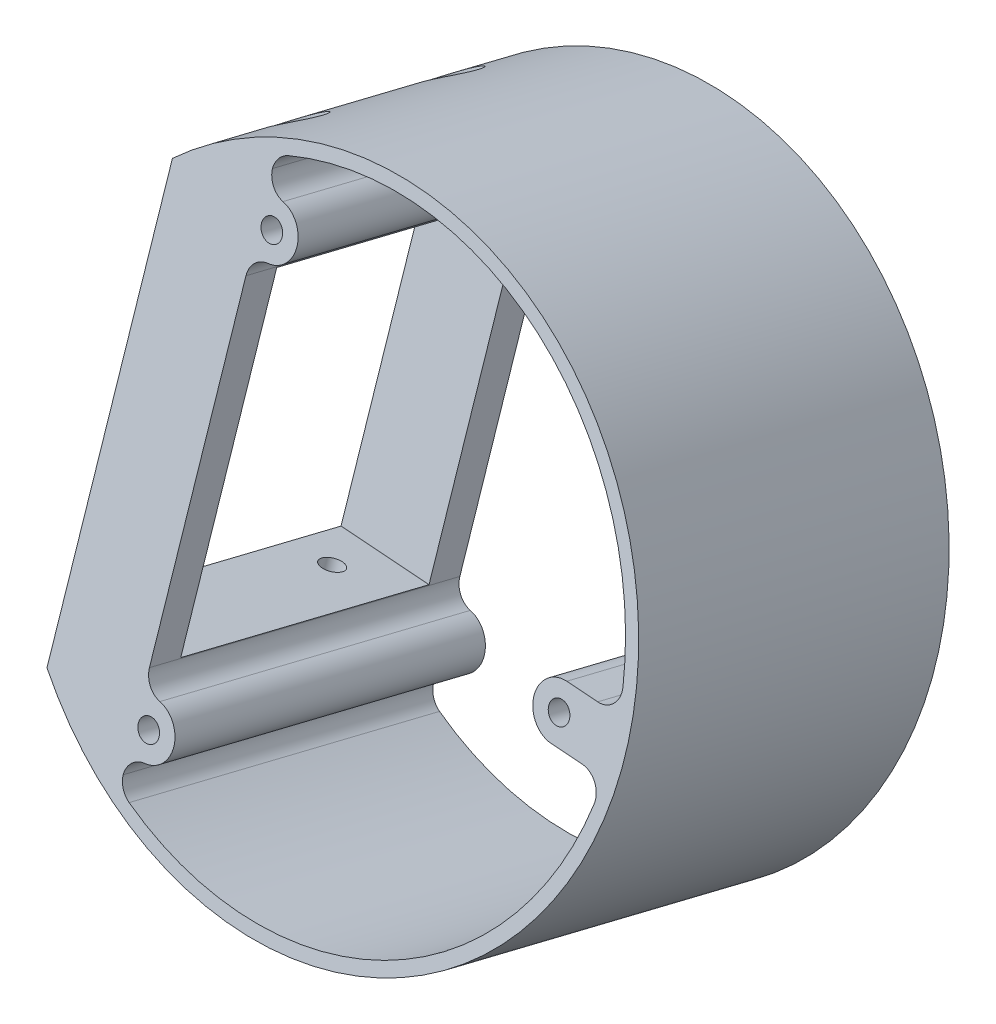
SolidWorks part; units mm, degrees
ref_plane "Front Plane" through (0, 0, 0) normal (0, 0, 1) x (1, 0, 0)
ref_plane "Top Plane" through (0, 0, 0) normal (0, 1, 0) x (1, 0, 0)
ref_plane "Right Plane" through (0, 0, 0) normal (1, 0, 0) x (0, 0, -1)
sketch "Sketch1" plane through (0, -11.0837, -45.1368) normal (0, -0.2385, -0.9711) x (-1, 0, 0)
  line L0 (190.5723, 100.5223) -> (195.806, 17.0201)
  line L1 (188.6521, 99.1867) -> (188.972, 94.0836)
  line L2 (133.8057, 55.0492) -> (125.3224, 54.5175) construction
  line L3 (133.5555, 59.0414) -> (125.248, 58.5207)
  line L4 (134.0559, 51.057) -> (125.7484, 50.5363)
  line L5 (189.4054, 87.169) -> (192.9808, 30.1232)
  line L6 (188.6521, 99.1867) -> (193.7341, 18.1055) construction
  line L7 (193.4142, 23.2086) -> (193.7341, 18.1055)
  arc A0 (188.972, 94.0836) -> (189.4054, 87.169) centre (187.1926, 90.5012) ccw
  circle A1 centre (191.2015, 26.5408) radius 1.65
  circle A2 centre (191.2015, 26.5408) radius 1.65
  circle A3 centre (133.8057, 55.0492) radius 1.65
  circle A4 centre (133.8057, 55.0492) radius 1.65
  circle A5 centre (187.1926, 90.5012) radius 1.65
  circle A6 centre (187.1926, 90.5012) radius 1.65
  arc A7 (192.9808, 30.1232) -> (193.4142, 23.2086) centre (191.2015, 26.5408) ccw
  arc A8 (134.0559, 51.057) -> (133.5555, 59.0414) centre (133.8057, 55.0492) ccw
  circle A9 centre (170.7333, 57.3637) radius 47.5 construction
  arc A10 (190.5723, 100.5223) -> (195.806, 17.0201) centre (170.7333, 57.3637) ccw
  arc A11 (188.6521, 99.1867) -> (125.248, 58.5207) centre (170.7333, 57.3637) ccw
  arc A12 (125.7484, 50.5363) -> (193.7341, 18.1055) centre (170.7333, 57.3637) ccw
  arc A13 (188.6521, 99.1867) -> (193.7341, 18.1055) centre (170.7333, 57.3637) ccw construction
  dimension "D4" = 8
  dimension "D1" = 0
  dimension "D2" = 0
  dimension "D3" = 0
  dimension "D5" = 2
extrude "Boss-Extrude1" add sketch "Sketch1" along normal blind 50
fillet "Fillet1" radius 3 8 edges at (-125.7484, 32.0328, -81.4671) (-125.248, 39.7867, -83.3711) (-188.972, 74.3236, -91.852) (-189.4054, 67.6085, -90.203) (-188.6521, 79.2796, -93.0689) (-192.9808, 12.2086, -76.5991) (-193.4142, 5.4935, -74.9501) (-193.7341, 0.5376, -73.7332)
sketch "Sketch2" plane through (-196.1024, 11.9366, -2.9311) normal (-0.998, 0.0607, -0.0149) x (-0.0122, -0.4224, -0.9063)
  line L0 (36.5364, -54.7188) -> (85.5823, -64.4399) construction
  line L1 (44.6696, -13.6841) -> (28.4031, -95.7536) construction
  line L2 (93.7155, -23.4051) -> (77.4491, -105.4746) construction
  line L3 (27.3014, -101.3124) -> (45.7714, -8.1252) construction
  line L4 (36.5804, -80.2139) -> (75.8172, -87.9907)
  line L5 (36.5804, -80.2139) -> (46.3015, -31.168)
  line L6 (46.3015, -31.168) -> (85.5382, -38.9448)
  line L7 (75.8172, -87.9907) -> (85.5382, -38.9448)
  line L8 (36.5804, -80.2139) -> (85.5382, -38.9448) construction
  line L9 (46.3015, -31.168) -> (75.8172, -87.9907) construction
  point P6 (61.0593, -59.5793)
  dimension "D1" = 40
  dimension "D2" = 50
extrude "Cut-Extrude1" cut sketch "Sketch2" against normal up to surface (2 mm away) up to face at (-191.1931, 39.9086, -83.401)
sketch "Sketch5" plane through (0, -11.0837, -45.1368) normal (0, 0.2385, 0.9711) x (1, 0, 0)
  line L0 (-194.7531, 33.8202) -> (-206.7296, 34.5708)
  line L1 (-191.6253, 83.7223) -> (-203.6018, 84.4729)
  line L2 (-206.7296, 34.5708) -> (-207.2081, 26.9362)
  line L3 (-203.6018, 84.4729) -> (-203.1233, 92.1076)
  line L4 (-189.6292, 83.5971) -> (-191.6253, 83.7223)
  line L5 (-191.6253, 83.7223) -> (-194.7531, 33.8202)
  line L6 (-194.7531, 33.8202) -> (-192.757, 33.6951)
  line L7 (-192.757, 33.6951) -> (-189.6292, 83.5971)
  line L8 (-189.6292, 83.5971) -> (-191.6253, 83.7223) construction
  line L9 (-191.6253, 83.7223) -> (-194.7531, 33.8202) construction
  line L10 (-194.7531, 33.8202) -> (-192.757, 33.6951) construction
  line L11 (-192.757, 33.6951) -> (-189.6292, 83.5971) construction
  line L12 (-194.7531, 33.8202) -> (-195.806, 17.0201)
  line L13 (-190.5723, 100.5223) -> (-191.6253, 83.7223)
  circle A0 centre (-170.7333, 57.3637) radius 47.5 construction
  arc A1 (-195.806, 17.0201) -> (-190.5723, 100.5223) centre (-170.7333, 57.3637) ccw construction
  arc A2 (-207.2081, 26.9362) -> (-195.806, 17.0201) centre (-170.7333, 57.3637) ccw
  arc A3 (-203.1233, 92.1076) -> (-190.5723, 100.5223) centre (-170.7333, 57.3637) cw
  dimension "D2" = 12
  dimension "D1" = 0
extrude "Boss-Extrude2" add sketch "Sketch5" against normal up to surface (50 mm away) up to face at (-133.8057, 32.056, -107.2155)
sketch "Sketch6" plane through (4.4771, 69.3702, -17.0344) normal (-0.0626, -0.9692, 0.238) x (0.998, -0.0607, 0.0149)
  line L0 (-196.4872, -51.4777) -> (-208.4872, -51.4777) construction
  line L1 (-208.4872, -96.4777) -> (-208.4872, -46.4777) construction
  line L2 (-202.4872, -46.4777) -> (-202.4872, -96.4777) construction
  line L3 (-208.4872, -46.4777) -> (-196.4872, -46.4777) construction
  line L4 (-208.4872, -96.4777) -> (-196.4872, -96.4777) construction
  line L5 (-202.4872, -83.9777) -> (-202.4872, -58.9777) construction
  circle A0 centre (-202.4872, -58.9777) radius 1.65
  circle A1 centre (-202.4872, -83.9777) radius 1.65
  point P7 (-202.4872, -51.4777)
  point P14 (-202.4872, -71.4777)
  point P16 (-202.4872, -71.4777)
  dimension "D1" = 3.3
  dimension "D2" = 3.3
  dimension "D3" = 25
extrude "Cut-Extrude2" cut sketch "Sketch6" against normal through all both and the other way through all
ref_plane "Plane1" through (4.9556, 76.7846, -18.8551) normal (-0.0626, -0.9692, 0.238) x (-0.998, 0.0607, -0.0149)
sketch "Sketch7" plane through (4.9556, 76.7846, -18.8551) normal (-0.0626, -0.9692, 0.238) x (-0.998, 0.0607, -0.0149)
  circle A0 centre (202.4872, 83.9777) radius 3.25
  circle A1 centre (202.4872, 58.9777) radius 3.25
  dimension "D1" = 6.5
extrude "Cut-Extrude3" cut sketch "Sketch7" against normal through all
ref_plane "Plane2" through (2.9132, 45.139, -11.0843) normal (-0.0626, -0.9692, 0.238) x (-0.998, 0.0607, -0.0149)
mirror "Mirror1" about plane through (2.9132, 45.139, -11.0843) normal (-0.0626, -0.9692, 0.238) of "Cut-Extrude3"
sketch "Sketch9" plane through (-196.1024, 11.9366, -2.9311) normal (-0.998, 0.0607, -0.0149) x (-0.0137, 0.0203, 0.9997)
  line L0 (-65.911, 58.5502) -> (-54.9536, 9.7657) construction
  line L1 (-54.9536, 9.7657) -> (-50.0752, 10.8614) construction
  line L2 (-50.0752, 10.8614) -> (-61.0325, 59.646) construction
  line L3 (-61.0325, 59.646) -> (-65.911, 58.5502) construction
  line L4 (-109.8171, 48.6886) -> (-98.8598, -0.096) construction
  line L5 (-98.8598, -0.096) -> (-93.9813, 0.9998) construction
  line L6 (-93.9813, 0.9998) -> (-104.9387, 49.7843) construction
  line L7 (-104.9387, 49.7843) -> (-109.8171, 48.6886) construction
  line L8 (-65.911, 58.5502) -> (-54.9536, 9.7657)
  line L9 (-54.9536, 9.7657) -> (-50.0752, 10.8614)
  line L10 (-50.0752, 10.8614) -> (-61.0325, 59.646)
  line L11 (-61.0325, 59.646) -> (-65.911, 58.5502)
  line L12 (-109.8171, 48.6886) -> (-98.8598, -0.096)
  line L13 (-98.8598, -0.096) -> (-93.9813, 0.9998)
  line L14 (-93.9813, 0.9998) -> (-104.9387, 49.7843)
  line L15 (-104.9387, 49.7843) -> (-109.8171, 48.6886)
extrude "Boss-Extrude3" add sketch "Sketch9" along normal up to surface (12 mm away) up to face at (-203.3626, 68.6974, -90.4704)
